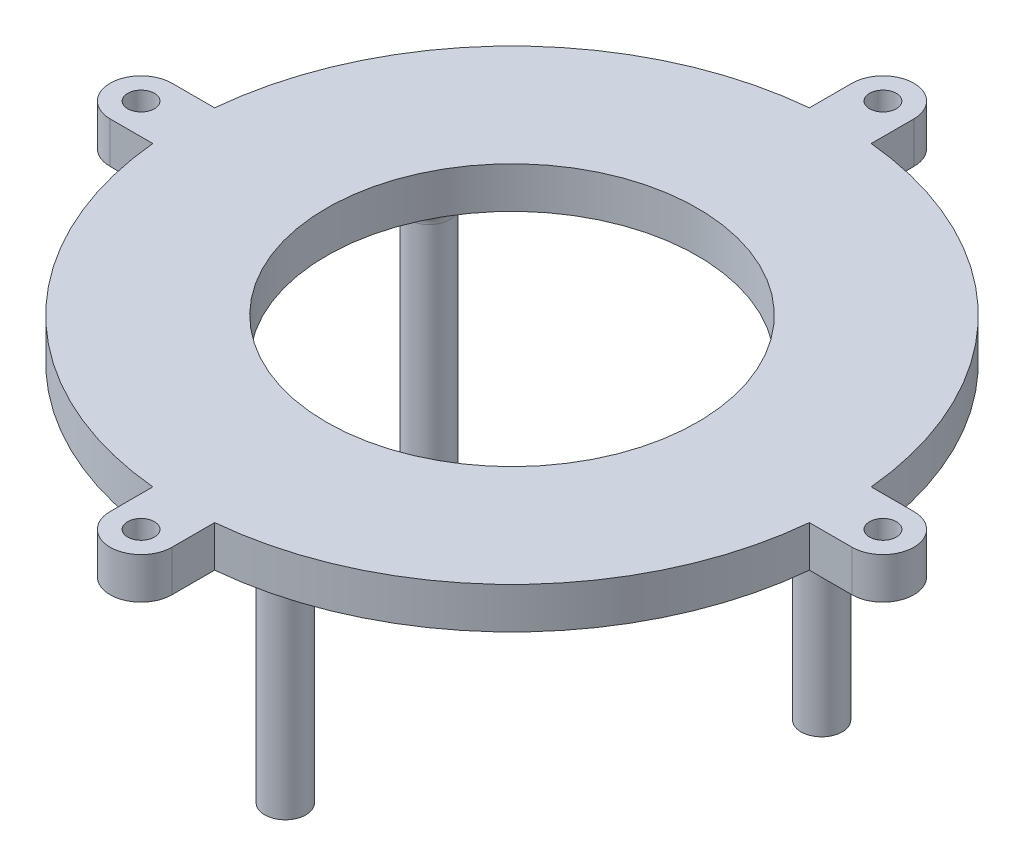
SolidWorks part; units mm, degrees
ref_plane "Front Plane" through (0, 0, 0) normal (0, 0, 1) x (1, 0, 0)
ref_plane "Top Plane" through (0, 0, 0) normal (0, 1, 0) x (1, 0, 0)
ref_plane "Right Plane" through (0, 0, 0) normal (1, 0, 0) x (0, 0, -1)
ref_axis "Center Axis" through (0, 0.65, 0) along (0, -1, 0)
sketch "STR Point" plane through (0, 0, 0) normal (0, 1, 0) x (1, 0, 0)
  point P0 (0.8, 2.9)
  dimension "D1" = 0.8
  dimension "D2" = 2.9
ref_axis "STR Axis" through (0.8, 0, -2.9) along (0, 1, 0)
sketch "Sketch1" plane through (0, 0, 0) normal (0, 1, 0) x (1, 0, 0)
  circle A0 centre (0, -11) radius 1
  dimension "D1" = 11
extrude "Boss-Extrude1" add sketch "Sketch1" against normal blind 13
sketch "Sketch2" plane through (0, 0, 0) normal (0, 1, 0) x (1, 0, 0)
  line L3 (-18, 1.5) -> (-15.9295, 1.5)
  line L4 (-18, -1.5) -> (-15.9295, -1.5)
  line L7 (1.5, 18) -> (1.5, 15.9295)
  line L8 (-1.5, 18) -> (-1.5, 15.9295)
  line L9 (18, 1.5) -> (15.9295, 1.5)
  line L10 (18, -1.5) -> (15.9295, -1.5)
  line L11 (1.5, -18) -> (1.5, -15.9295)
  line L12 (-1.5, -18) -> (-1.5, -15.9295)
  arc A0 (-15.9295, -1.5) -> (-1.5, -15.9295) centre (0, 0) ccw
  circle A1 centre (0, 0) radius 9
  arc A3 (-18, 1.5) -> (-18, -1.5) centre (-18, 0) ccw
  arc A4 (1.5, 18) -> (-1.5, 18) centre (0, 18) ccw
  arc A5 (18, -1.5) -> (18, 1.5) centre (18, 0) ccw
  arc A6 (-1.5, -18) -> (1.5, -18) centre (0, -18) ccw
  arc A7 (1.5, -15.9295) -> (15.9295, -1.5) centre (0, 0) ccw
  arc A8 (15.9295, 1.5) -> (1.5, 15.9295) centre (0, 0) ccw
  arc A9 (-1.5, 15.9295) -> (-15.9295, 1.5) centre (0, 0) ccw
  circle A10 centre (0, 18) radius 0.65
  circle A11 centre (18, 0) radius 0.65
  circle A12 centre (-18, 0) radius 0.65
  circle A13 centre (0, -18) radius 0.65
extrude "Boss-Extrude2" add sketch "Sketch2" along normal blind 2
pattern_circular "CirPattern2" count 3 over 360 about axis through (0, 0.65, 0) along (0, -1, 0) of "Boss-Extrude1" reverse direction yes
fillet "Fillet1" radius 1 3 edges at (10.3923, 0, -6) (0, 0, 12) (-10.3923, 0, -6)
